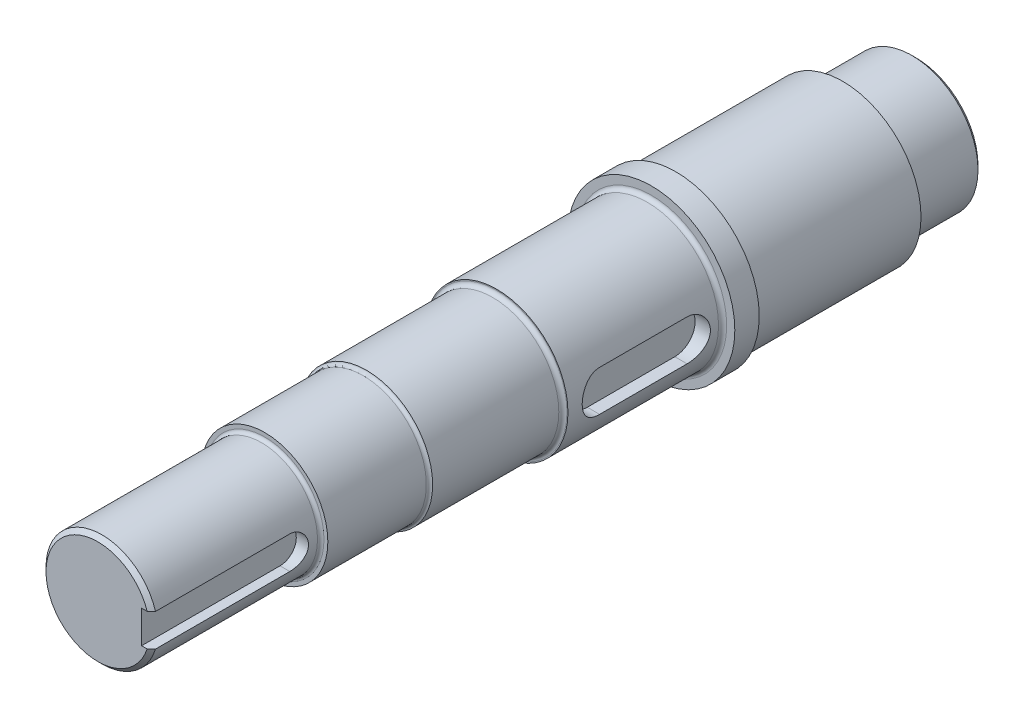
SolidWorks part; units mm, degrees
ref_plane "前视基准面" through (0, 0, 0) normal (0, 0, 1) x (1, 0, 0)
ref_plane "上视基准面" through (0, 0, 0) normal (0, 1, 0) x (1, 0, 0)
ref_plane "右视基准面" through (0, 0, 0) normal (1, 0, 0) x (0, 0, -1)
sketch "草图1" plane through (0, 0, 0) normal (0, 0, 1) x (1, 0, 0)
  circle A0 centre (0, 0) radius 32.5
  dimension "D1" = 65
extrude "凸台-拉伸1" add sketch "草图1" along normal blind 36
sketch "草图2" plane through (0, 0, 36) normal (0, 0, 1) x (1, 0, 0)
  circle A0 centre (0, 0) radius 38.5
  dimension "D1" = 77
extrude "凸台-拉伸2" add sketch "草图2" along normal blind 82
sketch "草图3" plane through (0, 0, 118) normal (0, 0, 1) x (1, 0, 0)
  circle A0 centre (0, 0) radius 41
  dimension "D1" = 82
extrude "凸台-拉伸3" add sketch "草图3" along normal blind 12
sketch "草图4" plane through (0, 0, 130) normal (0, 0, 1) x (1, 0, 0)
  circle A0 centre (0, 0) radius 35
  dimension "D1" = 70
extrude "凸台-拉伸4" add sketch "草图4" along normal blind 76
sketch "草图5" plane through (0, 0, 206) normal (0, 0, 1) x (1, 0, 0)
  circle A0 centre (0, 0) radius 32.5
  dimension "D1" = 65
extrude "凸台-拉伸5" add sketch "草图5" along normal blind 64
sketch "草图6" plane through (0, 0, 270) normal (0, 0, 1) x (1, 0, 0)
  circle A0 centre (0, 0) radius 31
  dimension "D1" = 62
extrude "凸台-拉伸6" add sketch "草图6" along normal blind 50
sketch "草图7" plane through (0, 0, 320) normal (0, 0, 1) x (1, 0, 0)
  circle A0 centre (0, 0) radius 27.5
  dimension "D1" = 55
extrude "凸台-拉伸7" add sketch "草图7" along normal blind 82
fillet "圆角1" radius 2 2 edges at (32.5, 0, 206) (35, 0, 130)
fillet "圆角2" radius 1.6 2 edges at (27.5, 0, 320) (31, 0, 270)
chamfer "倒角1" distance 2 angle 45 2 edges at (32.5, 0, 0) (27.5, 0, 402)
ref_plane "基准面1" through (27.5, 0, 0) normal (1, 0, 0) x (0, 0, -1)
sketch "草图8" plane through (27.5, 0, 0) normal (1, 0, 0) x (0, 0, -1)
  line L0 (-202.5, 0) -> (-135.849, 0) construction
  line L1 (-130, 37) -> (-130, -37) construction
  line L2 (-189, 10) -> (-146, 10)
  line L4 (-189, -10) -> (-146, -10)
  arc A0 (-146, -10) -> (-146, 10) centre (-146, 0) ccw
  arc A1 (-189, 10) -> (-189, -10) centre (-189, 0) ccw
  dimension "D4" = 20
  dimension "D5" = 20
  dimension "D1" = 20
  dimension "D2" = 10
  dimension "D3" = 43
  dimension "D6" = 16
extrude "切除-拉伸1" cut sketch "草图8" along normal blind 29
ref_plane "基准面2" through (21.5, 0, 0) normal (1, 0, 0) x (0, 0, -1)
sketch "草图9" plane through (21.5, 0, 0) normal (1, 0, 0) x (0, 0, -1)
  line L0 (-409.335, 0) -> (-328.903, 0) construction
  line L1 (-402, 25.5) -> (-402, -25.5) construction
  line L2 (-402, 8) -> (-334, 8)
  line L3 (-402, 8) -> (-402, -8)
  line L4 (-402, -8) -> (-334, -8)
  arc A0 (-334, -8) -> (-334, 8) centre (-334, 0) ccw
  dimension "D1" = 8
  dimension "D2" = 16
  dimension "D3" = 68
extrude "切除-拉伸2" cut sketch "草图9" along normal blind 20
